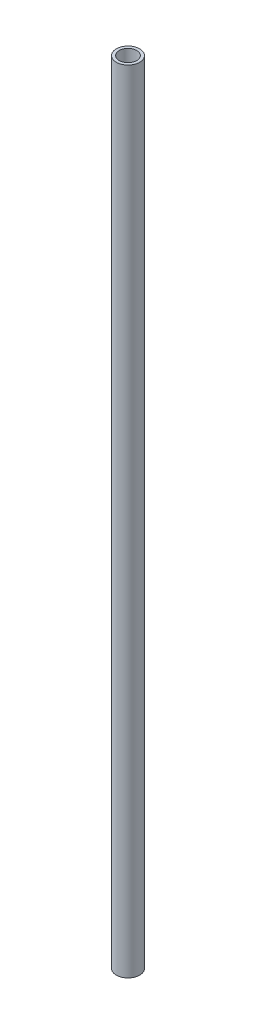
SolidWorks part; units mm, degrees
ref_plane "Front Plane" through (0, 0, 0) normal (0, 0, 1) x (1, 0, 0)
ref_plane "Top Plane" through (0, 0, 0) normal (0, 1, 0) x (1, 0, 0)
ref_plane "Right Plane" through (0, 0, 0) normal (1, 0, 0) x (0, 0, -1)
sketch "Sketch1" plane through (0, 0, 0) normal (0, 1, 0) x (1, 0, 0)
  circle A0 centre (0, 0) radius 6.35
  circle A1 centre (0, 0) radius 4.7625
  dimension "D1" = 1.5875
  dimension "D2" = 12.7
extrude "Boss-Extrude1" add sketch "Sketch1" along normal blind 429.895
